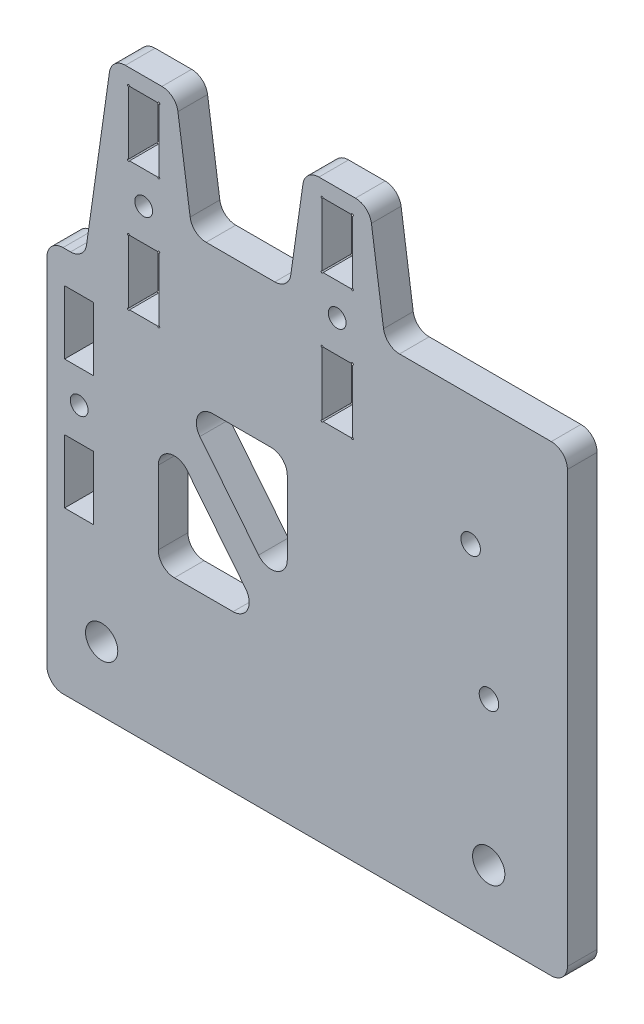
SolidWorks part; units mm, degrees
ref_plane "Front Plane" through (0, 0, 0) normal (0, 0, 1) x (1, 0, 0)
ref_plane "Top Plane" through (0, 0, 0) normal (0, 1, 0) x (1, 0, 0)
ref_plane "Right Plane" through (0, 0, 0) normal (1, 0, 0) x (0, 0, -1)
sketch "Sketch1" plane through (0, 0, 0) normal (0, 0, 1) x (1, 0, 0)
  line L0 (-40.2246, 5.8803) -> (-40.2246, -38.4697) construction
  line L1 (51.8504, -38.4697) -> (-46.5746, -38.4697)
  line L3 (-46.5746, 34.5553) -> (-46.5746, 52.6159)
  line L4 (-46.5746, -38.4697) -> (-46.5746, 34.5553)
  line L5 (51.8504, -38.4697) -> (-46.5746, 34.5553) construction
  line L6 (42.1271, 34.7961) -> (-46.5746, -38.4697) construction
  line L7 (-43.0956, -6.6197) -> (-37.3536, -6.6197)
  line L8 (-43.0956, 18.7803) -> (-37.3536, 18.7803)
  line L9 (-43.0956, 18.7803) -> (-43.0956, 31.2803)
  line L10 (-43.0956, 31.2803) -> (-37.3536, 31.2803)
  line L11 (-37.3536, 18.7803) -> (-37.3536, 31.2803)
  line L12 (-43.0956, 18.7803) -> (-37.3536, 31.2803) construction
  line L13 (-43.0956, 31.2803) -> (-37.3536, 18.7803) construction
  line L14 (-43.0956, -6.6197) -> (-43.0956, 5.8803)
  line L15 (-43.0956, 5.8803) -> (-37.3536, 5.8803)
  line L16 (-37.3536, -6.6197) -> (-37.3536, 5.8803)
  line L17 (-43.0956, -6.6197) -> (-37.3536, 5.8803) construction
  line L18 (-43.0956, 5.8803) -> (-37.3536, -6.6197) construction
  line L19 (-46.5746, 52.6159) -> (51.8504, 52.6159)
  line L20 (51.8504, -25.7697) -> (-46.5746, -25.7697) construction
  line L21 (-40.2246, -0.3697) -> (-40.2246, 25.0303) construction
  line L24 (51.8504, 52.6159) -> (55.8972, 52.6159)
  line L26 (51.8504, -38.4697) -> (55.8972, -38.4697)
  line L27 (55.8972, 52.6159) -> (55.8972, -38.4697)
  circle A0 centre (-35.7968, -25.7697) radius 3.175
  circle A1 centre (40.4032, -25.7697) radius 3.175
  circle A2 centre (-40.2246, 12.3303) radius 1.7526
  point P0 (0, 0)
  point P8 (-40.2246, 25.0303)
  point P14 (-40.2246, -0.3697)
  dimension "D10" = 6.35
  dimension "D13" = 3.5052
  dimension "D1" = 98.425
  dimension "D2" = 73.025
  dimension "D3" = 5.742
  dimension "D4" = 12.5
  dimension "D6" = 6.35
  dimension "D7" = 18.0606
  dimension "D8" = 15.494
  dimension "D12" = 10.7778
  dimension "D5" = 2
  dimension "D11" = 2
extrude "Boss-Extrude1" add sketch "Sketch1" along normal blind 5.842
sketch "Sketch2" plane through (0, 0, 5.842) normal (0, 0, 1) x (1, 0, 0)
  line L0 (55.8972, -38.4697) -> (55.8972, 52.6159) construction
  line L1 (-46.5746, -38.4697) -> (55.8972, -38.4697) construction
  line L2 (33.2912, 44.7153) -> (43.1972, 44.7153) construction
  line L3 (33.2912, -3.5447) -> (43.1972, -3.5447) construction
  line L4 (38.2442, -3.5447) -> (38.2442, 44.7153) construction
  line L6 (48.0747, 0.1423) -> (28.4136, 0.1423)
  line L7 (48.2732, 0.3408) -> (48.2732, 40.8299)
  line L8 (48.0747, 41.0283) -> (28.4136, 41.0283)
  line L9 (28.2152, 0.3408) -> (28.2152, 40.8299)
  line L10 (48.2732, 0.1423) -> (28.2152, 41.0283) construction
  line L11 (48.2732, 41.0283) -> (28.2152, 0.1423) construction
  circle A0 centre (43.1972, -3.5447) radius 1.7526
  circle A1 centre (33.2912, -3.5447) radius 1.7526
  circle A2 centre (43.1972, 44.7153) radius 1.7526
  circle A3 centre (33.2912, 44.7153) radius 1.7526
  arc A4 (48.0747, 0.1423) -> (48.2732, 0.3408) centre (48.2732, 0.1423) ccw
  arc A5 (48.2732, 40.8299) -> (48.0747, 41.0283) centre (48.2732, 41.0283) ccw
  arc A6 (28.2152, 40.8299) -> (28.4136, 41.0283) centre (28.2152, 41.0283) cw
  arc A7 (28.4136, 0.1423) -> (28.2152, 0.3408) centre (28.2152, 0.1423) cw
  point P14 (38.2442, 20.5853)
  dimension "D1" = 3.5052
  dimension "D6" = 0.3969
  dimension "D7" = 0.3969
  dimension "D2" = 12.7
  dimension "D3" = 34.925
  dimension "D4" = 20.058
  dimension "D5" = 40.886
extrude "Cut-Extrude1" [suppressed] cut sketch "Sketch2" against normal through all
sketch "Sketch3" plane through (0, 0, 5.842) normal (0, 0, 1) x (1, 0, 0)
  line L0 (-46.5746, 39.9159) -> (55.8972, 39.9159) construction
  line L1 (-46.5746, 52.6159) -> (-46.5746, -38.4697) construction
  line L2 (55.8972, -38.4697) -> (55.8972, 52.6159) construction
  line L3 (55.8972, 52.6159) -> (-46.5746, 52.6159) construction
  line L4 (7.5909, 46.2659) -> (13.5599, 33.5659) construction
  line L5 (-24.7385, 33.5659) -> (-30.3106, 33.5659)
  line L6 (-24.5401, 33.7644) -> (-24.5401, 46.0675)
  line L7 (-24.7385, 46.2659) -> (-30.3106, 46.2659)
  line L8 (-30.5091, 33.7644) -> (-30.5091, 46.0675)
  line L9 (-24.5401, 33.5659) -> (-30.5091, 46.2659) construction
  line L10 (-8.4746, 52.6159) -> (-8.4746, 39.9159) construction
  line L11 (-24.5401, 46.2659) -> (-30.5091, 33.5659) construction
  line L12 (7.5909, 33.5659) -> (13.5599, 46.2659) construction
  line L13 (13.5599, 33.7644) -> (13.5599, 46.0675)
  line L14 (7.7894, 46.2659) -> (13.3615, 46.2659)
  line L15 (7.5909, 33.7644) -> (7.5909, 46.0675)
  line L16 (7.7894, 33.5659) -> (13.3615, 33.5659)
  arc A0 (-24.7385, 33.5659) -> (-24.5401, 33.7644) centre (-24.5401, 33.5659) ccw
  arc A1 (-30.5091, 33.7644) -> (-30.3106, 33.5659) centre (-30.5091, 33.5659) ccw
  arc A2 (-24.7385, 46.2659) -> (-24.5401, 46.0675) centre (-24.5401, 46.2659) cw
  arc A3 (-30.5091, 46.0675) -> (-30.3106, 46.2659) centre (-30.5091, 46.2659) cw
  arc A4 (13.5599, 46.0675) -> (13.3615, 46.2659) centre (13.5599, 46.2659) ccw
  arc A5 (7.7894, 46.2659) -> (7.5909, 46.0675) centre (7.5909, 46.2659) ccw
  arc A6 (13.5599, 33.7644) -> (13.3615, 33.5659) centre (13.5599, 33.5659) cw
  arc A7 (7.7894, 33.5659) -> (7.5909, 33.7644) centre (7.5909, 33.5659) cw
  point P6 (-27.5246, 39.9159)
  point P7 (-27.5246, 39.9159)
  point P39 (10.5754, 39.9159)
  dimension "D3" = 0.3969
  dimension "D4" = 0.3969
  dimension "D1" = 5.969
  dimension "D2" = 12.7
  dimension "D5" = 12.7
  dimension "D6" = 19.05
  dimension "D9" = 19.05
extrude "Cut-Extrude2" cut sketch "Sketch3" against normal through all
sketch "Sketch4" plane through (0, 0, 5.842) normal (0, 0, 1) x (1, 0, 0)
  line L0 (-30.5091, 39.9159) -> (13.5599, 39.9159) construction
  line L3 (10.5754, 39.9159) -> (10.5754, 65.3159) construction
  line L4 (-8.4746, 39.9159) -> (-8.4746, 46.2659) construction
  line L5 (1.0366, 52.6159) -> (4.2254, 74.8409)
  line L6 (13.3615, 71.6659) -> (7.7894, 71.6659)
  line L7 (13.5599, 71.4675) -> (13.5599, 59.1644)
  line L8 (13.3615, 58.9659) -> (7.7894, 58.9659)
  line L9 (7.5909, 71.4675) -> (7.5909, 59.1644)
  line L10 (13.5599, 71.6659) -> (7.5909, 58.9659) construction
  line L11 (13.5599, 58.9659) -> (7.5909, 71.6659) construction
  line L12 (55.8972, 52.6159) -> (-46.5746, 52.6159) construction
  line L13 (4.2254, 74.8409) -> (16.9254, 74.8409)
  line L14 (16.9254, 74.8409) -> (20.0866, 52.6159)
  line L15 (20.0866, 52.6159) -> (1.0366, 52.6159)
  line L16 (-30.5091, 58.9659) -> (-24.5401, 71.6659) construction
  line L17 (-30.5091, 71.6659) -> (-24.5401, 58.9659) construction
  line L18 (-37.0358, 52.6159) -> (-17.9858, 52.6159)
  line L19 (-33.8746, 74.8409) -> (-37.0358, 52.6159)
  line L20 (-21.1746, 74.8409) -> (-33.8746, 74.8409)
  line L21 (-24.5401, 71.4675) -> (-24.5401, 59.1644)
  line L22 (-30.3106, 58.9659) -> (-24.7385, 58.9659)
  line L23 (-30.5091, 71.4675) -> (-30.5091, 59.1644)
  line L24 (-30.3106, 71.6659) -> (-24.7385, 71.6659)
  line L25 (-17.9858, 52.6159) -> (-21.1746, 74.8409)
  line L26 (13.5599, 33.7644) -> (13.5599, 46.0675) construction
  line L27 (-30.5091, 46.0675) -> (-30.5091, 33.7644) construction
  arc A0 (13.5599, 71.4675) -> (13.3615, 71.6659) centre (13.5599, 71.6659) ccw
  arc A1 (13.3615, 58.9659) -> (13.5599, 59.1644) centre (13.5599, 58.9659) ccw
  arc A2 (7.7894, 58.9659) -> (7.5909, 59.1644) centre (7.5909, 58.9659) cw
  arc A3 (7.5909, 71.4675) -> (7.7894, 71.6659) centre (7.5909, 71.6659) cw
  arc A4 (-24.5401, 71.4675) -> (-24.7385, 71.6659) centre (-24.5401, 71.6659) ccw
  arc A5 (-30.5091, 71.4675) -> (-30.3106, 71.6659) centre (-30.5091, 71.6659) cw
  arc A6 (-24.7385, 58.9659) -> (-24.5401, 59.1644) centre (-24.5401, 58.9659) ccw
  arc A7 (-30.3106, 58.9659) -> (-30.5091, 59.1644) centre (-30.5091, 58.9659) cw
  point P20 (10.5754, 74.8409)
  point P29 (-27.5246, 74.8409)
  dimension "D7" = 0.3969
  dimension "D8" = 0.3969
  dimension "D1" = 25.4
  dimension "D2" = 12.7
  dimension "D3" = 5.969
  dimension "D4" = 9.525
  dimension "D5" = 12.7
  dimension "D6" = 19.05
extrude "Boss-Extrude2" add sketch "Sketch4" against normal up to surface (5.842 mm away) up to face at (10.5754, 39.9159, 0)
fillet "Fillet1" radius 3.175 7 edges at (16.9254, 74.8409, 2.921) (4.2254, 74.8409, 2.921) (-17.9858, 52.6159, 2.921) (-21.1746, 74.8409, 2.921) (-33.8746, 74.8409, 2.921)
sketch "Sketch5" plane through (0, 0, 5.842) normal (0, 0, 1) x (1, 0, 0)
  line L0 (-27.5246, 71.6659) -> (-27.5246, 33.5659) construction
  line L1 (-24.7385, 71.6659) -> (-30.3106, 71.6659) construction
  line L2 (-30.3106, 33.5659) -> (-24.7385, 33.5659) construction
  line L3 (10.5754, 71.6659) -> (10.5754, 33.5659) construction
  line L4 (13.3615, 71.6659) -> (7.7894, 71.6659) construction
  line L5 (7.7894, 33.5659) -> (13.3615, 33.5659) construction
  circle A0 centre (-27.5246, 52.6159) radius 1.7526
  circle A1 centre (10.5754, 52.6159) radius 1.7526
  dimension "D1" = 3.5052
  dimension "D2" = 3.5052
extrude "Cut-Extrude3" cut sketch "Sketch5" against normal through all
sketch "Sketch6" plane through (0, 0, 5.842) normal (0, 0, 1) x (1, 0, 0)
  line L0 (-37.0358, 52.6159) -> (-39.1672, 37.6303)
  line L1 (-34.2626, 72.113) -> (-37.0358, 52.6159) construction
  line L2 (-37.3536, 31.2803) -> (-43.0956, 31.2803) construction
  line L3 (-39.1672, 37.6303) -> (-46.5746, 37.6303)
  line L4 (-46.5746, 52.6159) -> (-46.5746, -38.4697) construction
  line L5 (-46.5746, 37.6303) -> (-46.5746, 52.6159)
  line L6 (-46.5746, 52.6159) -> (-37.0358, 52.6159)
  dimension "D1" = 6.35
extrude "Cut-Extrude4" cut sketch "Sketch6" against normal through all
fillet "Fillet2" radius 3.175 5 edges at (-39.1672, 37.6303, 2.921) (-46.5746, 37.6303, 2.921) (-46.5746, -38.4697, 2.921) (55.8972, 52.6159, 2.921) (55.8972, -38.4697, 2.921)
sketch "Sketch7" [suppressed] plane through (0, 0, 5.842) normal (0, 0, 1) x (1, 0, 0)
  line L0 (6.4764, -22.5947) -> (19.1764, -22.5947) construction
  line L1 (6.4764, -19.4197) -> (19.1764, -19.4197)
  line L2 (6.4764, -25.7697) -> (19.1764, -25.7697)
  line L3 (-43.3996, -38.4697) -> (52.7222, -38.4697) construction
  arc A0 (6.4764, -19.4197) -> (6.4764, -25.7697) centre (6.4764, -22.5947) ccw
  arc A1 (19.1764, -25.7697) -> (19.1764, -19.4197) centre (19.1764, -22.5947) ccw
  point P2 (12.8264, -22.5947)
  dimension "D3" = 3.175
  dimension "D1" = 12.7
  dimension "D2" = 12.7
extrude "Cut-Extrude5" [suppressed] cut sketch "Sketch7" against normal through all
sketch "Sketch8" [suppressed] plane through (0, 0, 5.842) normal (0, 0, 1) x (1, 0, 0)
  line L0 (17.7972, -38.4697) -> (17.7972, 37.7303) construction
  line L1 (-43.3996, -38.4697) -> (52.7222, -38.4697) construction
  line L2 (55.8972, -35.2947) -> (55.8972, 49.4409) construction
  line L3 (14.6222, 5.9803) -> (20.9722, 5.9803) construction
  line L4 (14.6222, 7.5678) -> (20.9722, 7.5678)
  line L5 (14.6222, 4.3928) -> (20.9722, 4.3928)
  line L6 (14.6222, 25.0303) -> (20.9722, 25.0303) construction
  line L7 (14.6222, 26.6178) -> (20.9722, 26.6178)
  line L8 (14.6222, 23.4428) -> (20.9722, 23.4428)
  arc A0 (14.6222, 7.5678) -> (14.6222, 4.3928) centre (14.6222, 5.9803) ccw
  arc A1 (20.9722, 4.3928) -> (20.9722, 7.5678) centre (20.9722, 5.9803) ccw
  arc A2 (14.6222, 26.6178) -> (14.6222, 23.4428) centre (14.6222, 25.0303) ccw
  arc A3 (20.9722, 23.4428) -> (20.9722, 26.6178) centre (20.9722, 25.0303) ccw
  point P8 (17.7972, 5.9803)
  point P17 (17.7972, 25.0303)
  dimension "D2" = 1.5875
  dimension "D1" = 38.1
  dimension "D3" = 6.35
  dimension "D4" = 76.2
  dimension "D5" = 2
  dimension "D6" = 44.45
extrude "Cut-Extrude6" [suppressed] cut sketch "Sketch8" against normal through all
sketch "Sketch9" [suppressed] plane through (0, 0, 5.842) normal (0, 0, 1) x (1, 0, 0)
  line L0 (3.3014, -22.5947) -> (-46.5746, -22.5947) construction
  line L1 (-46.5746, 34.4553) -> (-46.5746, -35.2947) construction
  line L2 (-15.7486, -25.7697) -> (-15.7486, -19.4197) construction
  line L3 (-17.3361, -25.7697) -> (-17.3361, -19.4197)
  line L4 (-14.1611, -25.7697) -> (-14.1611, -19.4197)
  line L5 (-3.0486, -25.7697) -> (-3.0486, -19.4197) construction
  line L6 (-4.6361, -25.7697) -> (-4.6361, -19.4197)
  line L7 (-1.4611, -25.7697) -> (-1.4611, -19.4197)
  arc A0 (6.4764, -19.4197) -> (6.4764, -25.7697) centre (6.4764, -22.5947) ccw construction
  arc A1 (-17.3361, -25.7697) -> (-14.1611, -25.7697) centre (-15.7486, -25.7697) ccw
  arc A2 (-14.1611, -19.4197) -> (-17.3361, -19.4197) centre (-15.7486, -19.4197) ccw
  arc A3 (-4.6361, -25.7697) -> (-1.4611, -25.7697) centre (-3.0486, -25.7697) ccw
  arc A4 (-1.4611, -19.4197) -> (-4.6361, -19.4197) centre (-3.0486, -19.4197) ccw
  point P10 (-15.7486, -22.5947)
  point P18 (-3.0486, -22.5947)
  dimension "D2" = 1.5875
  dimension "D1" = 6.35
  dimension "D3" = 19.05
extrude "Cut-Extrude7" [suppressed] cut sketch "Sketch9" against normal through all
sketch "Sketch10" plane through (0, 0, 5.842) normal (0, 0, 1) x (1, 0, 0)
  line L0 (-20.5876, 24.0409) -> (0.7464, 24.0409)
  line L1 (-30.3106, 33.5659) -> (-24.7385, 33.5659) construction
  line L2 (-24.6536, 18.9584) -> (-24.6536, -7.7091)
  line L3 (-37.3536, 18.7803) -> (-37.3536, 31.2803) construction
  line L4 (0.7464, 24.0409) -> (0.7464, -2.6266)
  line L5 (-3.3196, -7.7091) -> (-24.6536, -7.7091)
  line L7 (-24.6536, 18.9584) -> (-3.3196, -7.7091)
  line L8 (-20.5876, 24.0409) -> (0.7464, -2.6266)
  dimension "D1" = 9.525
  dimension "D2" = 12.7
extrude "Cut-Extrude8" cut sketch "Sketch10" against normal through all
fillet "Fillet3" radius 3.175 6 edges at (0.7464, 24.0409, 2.921) (0.7464, -2.6266, 2.921) (-20.5876, 24.0409, 2.921) (-24.6536, 18.9584, 2.921) (-24.6536, -7.7091, 2.921) (-3.3196, -7.7091, 2.921)
sketch "Sketch11" plane through (0, 0, 5.842) normal (0, 0, 1) x (1, 0, 0)
  line L0 (55.8972, -35.2947) -> (55.8972, 49.4409) construction
  line L1 (52.7222, 52.6159) -> (22.842, 52.6159) construction
  circle A0 centre (36.8472, 27.2159) radius 1.92
  circle A1 centre (40.4472, 2.5659) radius 1.92
  dimension "D1" = 3.84
  dimension "D2" = 3.84
  dimension "D3" = 3.6
  dimension "D4" = 24.65
  dimension "D5" = 19.05
  dimension "D6" = 25.4
extrude "Cut-Extrude9" cut sketch "Sketch11" against normal through all
